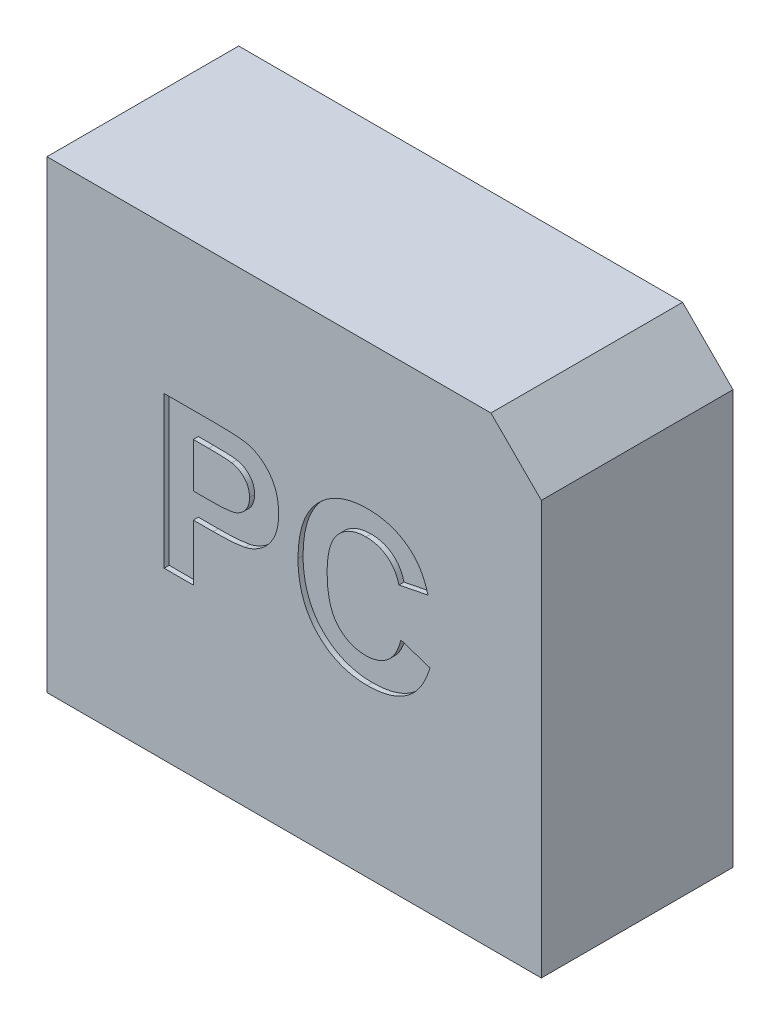
SolidWorks part; units mm, degrees
ref_plane "Front Plane" through (0, 0, 0) normal (0, 0, 1) x (1, 0, 0)
ref_plane "Top Plane" through (0, 0, 0) normal (0, 1, 0) x (1, 0, 0)
ref_plane "Right Plane" through (0, 0, 0) normal (1, 0, 0) x (0, 0, -1)
sketch "Sketch1" plane through (0, 0, 0) normal (0, 1, 0) x (1, 0, 0)
  line L1 (-245, 95) -> (245, 95)
  line L2 (-245, 95) -> (-245, -95)
  line L3 (-245, -95) -> (245, -95)
  line L4 (245, 95) -> (245, -95)
  line L5 (-245, 95) -> (245, -95) construction
  line L6 (-245, -95) -> (245, 95) construction
  point P0 (0, 0)
  dimension "D1" = 190
  dimension "D2" = 490
extrude "Boss-Extrude1" add sketch "Sketch1" along normal blind 460
sketch "Sketch2" plane through (0, 0, 95) normal (0, 0, 1) x (1, 0, 0)
  line L0 (-245, 164.8132) -> (245, 164.8132) construction
  line L1 (-245, 460) -> (-245, 0) construction
  line L2 (245, 460) -> (245, 0) construction
  text T0 "PC" font "Arial" height 150
  point P3 (-245, 164.3727)
  point P6 (245, 164.8132)
extrude "Cut-Extrude1" cut sketch "Sketch2" against normal blind 5
chamfer "Chamfer1" distance 50 angle 45 1 edges at (245, 460, 0)
